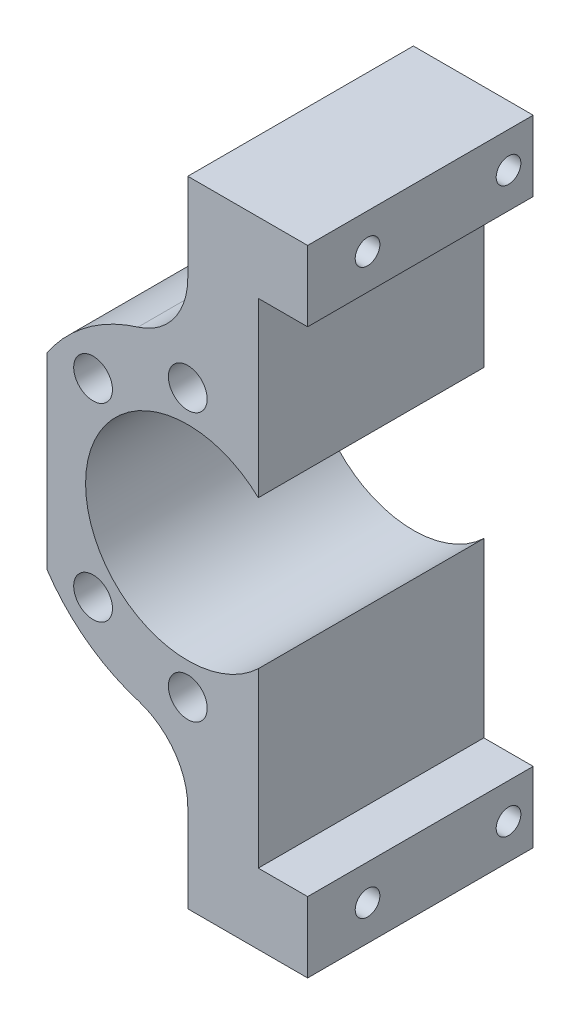
SolidWorks part; units mm, degrees
ref_plane "Plan de face" through (0, 0, 0) normal (0, 0, 1) x (1, 0, 0)
ref_plane "Plan de dessus" through (0, 0, 0) normal (0, 1, 0) x (1, 0, 0)
ref_plane "Plan de droite" through (0, 0, 0) normal (1, 0, 0) x (0, 0, -1)
sketch "Esquisse2" plane through (0, 0, 0) normal (0, 0, 1) x (1, 0, 0)
  line L1 (-22.3865, 12.0572) -> (-22.3865, -14.4758)
  line L2 (-2.3865, 22.7907) -> (7.6135, 22.7907)
  line L5 (7.6135, -25.2093) -> (-2.3865, -25.2093)
  line L6 (7.6135, -11.7093) -> (7.6135, -25.2093)
  line L7 (7.6135, 9.2907) -> (7.6135, 22.7907)
  arc A0 (7.6135, -11.7093) -> (7.6135, 9.2907) centre (-2.3865, -1.2093) cw
  arc A2 (-22.3865, 12.0572) -> (-2.3865, 22.7907) centre (-2.3865, -1.2093) cw
  arc A3 (-22.3865, -14.4758) -> (-2.3865, -25.2093) centre (-2.3865, -1.2093) ccw
  circle A4 centre (-2.3865, -1.2093) radius 19 construction
  circle A5 centre (-2.3865, 17.7907) radius 2.75
  circle A6 centre (-15.8215, 12.2258) radius 2.75
  circle A8 centre (-2.3865, -20.2093) radius 2.75
  circle A10 centre (-15.8215, -14.6443) radius 2.75
  dimension "D2" = 24
  dimension "D3" = 38
  dimension "D4" = 5.5
  dimension "D5" = 30
  dimension "D9" = 14.5
  dimension "D1" = 26.533
  dimension "D6" = 45
  dimension "D8" = 45
extrude "Boss.-Extru.1" add sketch "Esquisse2" along normal blind 32
sketch "Esquisse3" plane through (7.6135, 0, 0) normal (1, 0, 0) x (0, 0, -1)
  line L1 (0, 22.7907) -> (-32, 22.7907)
  line L2 (-32, 22.7907) -> (-32, 43.7907)
  line L3 (-32, 43.7907) -> (0, 43.7907)
  line L4 (0, 43.7907) -> (0, 22.7907)
  line L5 (0, -25.2093) -> (0, -11.7093) construction
  line L6 (-32, -25.2093) -> (0, -25.2093)
  line L7 (-32, -25.2093) -> (-32, -46.2093)
  line L8 (-32, -46.2093) -> (0, -46.2093)
  line L9 (0, -25.2093) -> (0, -46.2093)
  line L10 (-32, 22.7907) -> (-32, -25.2093) construction
  line L11 (-23.5, 38.7907) -> (-23.5, -41.2093) construction
  circle A0 centre (-23.5, 38.7907) radius 1.75
  circle A1 centre (-3.5, 38.7907) radius 1.75
  circle A2 centre (-23.5, -41.2093) radius 1.75
  circle A3 centre (-3.5, -41.2093) radius 1.75
  point P21 (-23.5, -1.2093)
  point P22 (-32, -1.2093)
  dimension "D1" = 3.5
  dimension "D2" = 20
  dimension "D3" = 80
  dimension "D4" = 5
  dimension "D5" = 3.5
extrude "Boss.-Extru.2" add sketch "Esquisse3" against normal up to vertex (10 mm away) up to point (-2.3865, 22.7907, 32)
sketch "Esquisse4" plane through (7.6135, 0, 0) normal (1, 0, 0) x (0, 0, -1)
  line L0 (0, 9.2907) -> (0, 43.7907) construction
  line L1 (-32, 43.7907) -> (0, 43.7907)
  line L2 (-32, 43.7907) -> (-32, 33.7907)
  line L3 (-32, 33.7907) -> (0, 33.7907)
  line L4 (0, 43.7907) -> (0, 33.7907)
  line L5 (0, -46.2093) -> (0, -11.7093) construction
  line L6 (-32, -46.2093) -> (0, -46.2093)
  line L7 (-32, -46.2093) -> (-32, -36.2093)
  line L8 (-32, -36.2093) -> (0, -36.2093)
  line L9 (0, -46.2093) -> (0, -36.2093)
  circle A0 centre (-3.5, -41.2093) radius 1.75 construction
  circle A1 centre (-23.5, -41.2093) radius 1.75 construction
  circle A2 centre (-3.5, 38.7907) radius 1.75 construction
  circle A3 centre (-23.5, 38.7907) radius 1.75 construction
  circle A4 centre (-3.5, -41.2093) radius 1.75
  circle A5 centre (-23.5, -41.2093) radius 1.75
  circle A6 centre (-3.5, 38.7907) radius 1.75
  circle A7 centre (-23.5, 38.7907) radius 1.75
  dimension "D1" = 10
extrude "Boss.-Extru.3" add sketch "Esquisse4" along normal blind 7
fillet "Congé1" radius 10 2 edges at (-2.3865, -25.2093, 16) (-2.3865, 22.7907, 16)
